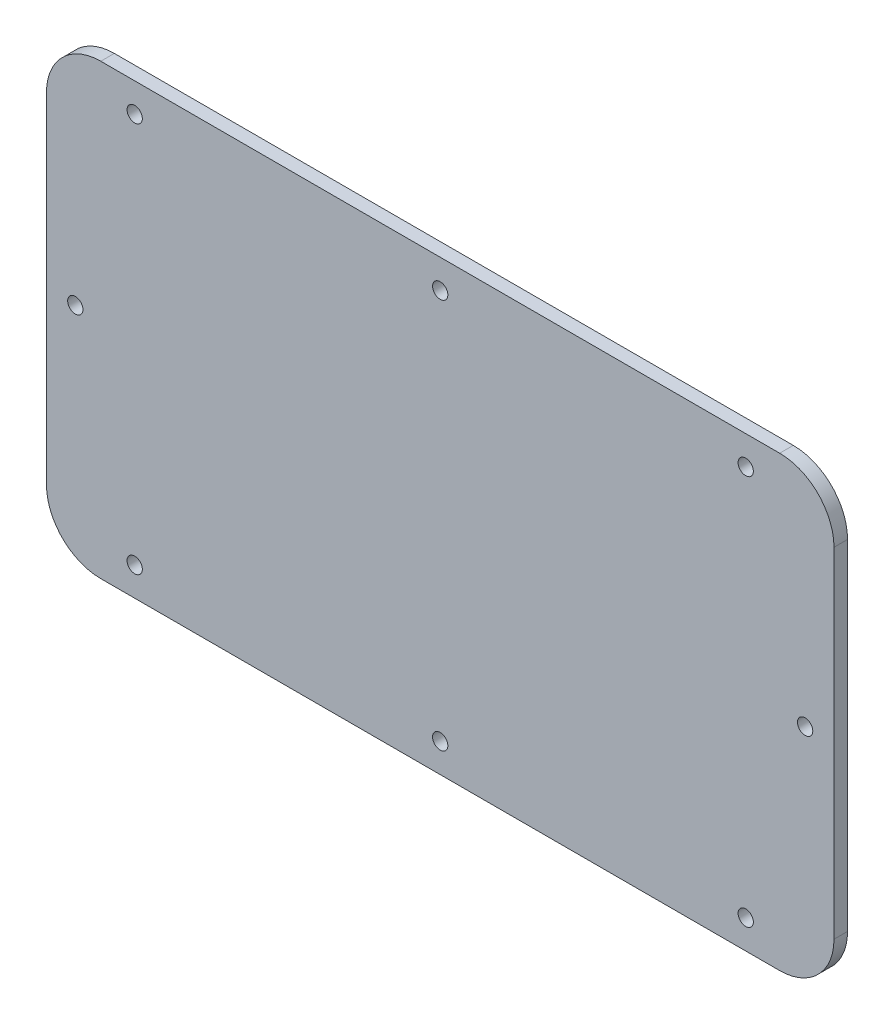
SolidWorks part; units mm, degrees
material "ПК/АБС"
ref_plane "Спереди" through (0, 0, 0) normal (0, 0, 1) x (1, 0, 0)
ref_plane "Сверху" through (0, 0, 0) normal (0, 1, 0) x (1, 0, 0)
ref_plane "Справа" through (0, 0, 0) normal (1, 0, 0) x (0, 0, -1)
sketch "Эскиз1" plane through (0, 0, 0) normal (0, 0, 1) x (1, 0, 0)
  line L0 (50, 0) -> (-50, 0) construction
  line L1 (116, -66) -> (-116, -66)
  line L2 (116, -66) -> (116, 66)
  line L3 (116, 66) -> (-116, 66)
  line L4 (-116, -66) -> (-116, 66)
  line L5 (116, -66) -> (-116, 66) construction
  line L6 (116, 66) -> (-116, -66) construction
  circle A0 centre (0, 57.5) radius 2.25
  circle A1 centre (-90, 57.5) radius 2.25
  circle A2 centre (90, 57.5) radius 2.25
  circle A3 centre (-107.5, 0) radius 2.25
  circle A4 centre (107.5, 0) radius 2.25
  circle A5 centre (90, -57.5) radius 2.25
  circle A6 centre (0, -57.5) radius 2.25
  circle A7 centre (-90, -57.5) radius 2.25
  point P0 (0, 0)
  dimension "D3" = 4.5
  dimension "D1" = 232
  dimension "D2" = 132
  dimension "D4" = 8.5
  dimension "D5" = 180
  dimension "D6" = 26
  dimension "D7" = 215
  dimension "D8" = 8.5
base flange "Базовая кромка1" sketch "Эскиз1" thickness 4 reverse thickness direction no parameters "D1"=3
fillet "Скругление1" radius 16 4 edges at (116, -66, -2) (116, 66, -2) (-116, -66, -2) (-116, 66, -2)
sketch "Сгиб-Линии1" [suppressed] plane through (0, 0, 0) normal (0, 1, 0) x (1, 0, 0)
sketch "Граничная рамка1" [suppressed] plane through (0, 0, 0) normal (0, 1, 0) x (1, 0, 0)
sheet metal parameters "Листовой металл3" thickness 4 parameters "D1"=3
flat pattern "Развертка3" [suppressed]
sketch "Сгиб-Линии2" plane through (0, 0, 0) normal (0, 1, 0) x (1, 0, 0)
sketch3d "Граничная рамка2" [suppressed]
  line L0 (-116, 66, 0) -> (116, 66, 0) construction
  line L1 (-116, -66, 0) -> (116, -66, 0) construction
  line L2 (-116, 66, 0) -> (-116, -66, 0) construction
  line L3 (116, 66, 0) -> (116, -66, 0) construction
